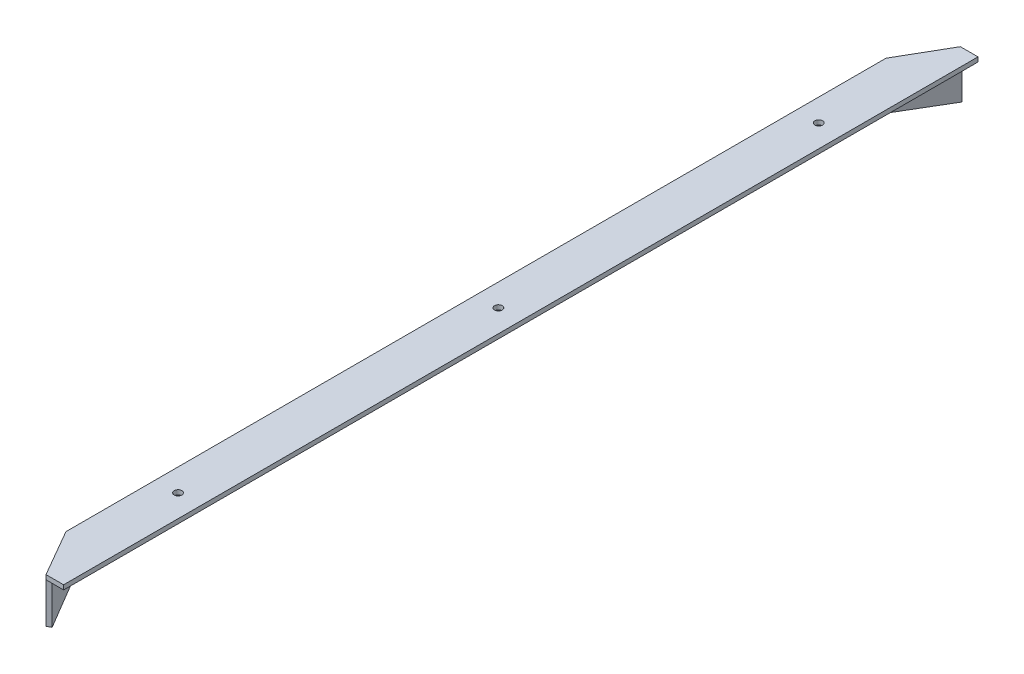
SolidWorks part; units mm, degrees
material "1.0116 (S235J2G3)"
ref_plane "Front Plane" through (0, 0, 0) normal (0, 0, 1) x (1, 0, 0)
ref_plane "Top Plane" through (0, 0, 0) normal (0, 1, 0) x (1, 0, 0)
ref_plane "Right Plane" through (0, 0, 0) normal (1, 0, 0) x (0, 0, -1)
sketch "Sketch1" plane through (0, 0, 0) normal (0, 0, 1) x (1, 0, 0)
  line L6 (0, 0) -> (0, 70)
  line L7 (0, 70) -> (70, 70)
  line L8 (70, 70) -> (70, 63)
  line L9 (70, 63) -> (7, 63)
  line L10 (7, 63) -> (7, 0)
  line L11 (7, 0) -> (0, 0)
  dimension "D1" = 70
  dimension "D2" = 70
  dimension "D3" = 7
  dimension "D4" = 7
extrude "Boss-Extrude1" add sketch "Sketch1" along normal blind 640
sketch "Sketch21" plane through (0, 0, 0) normal (0, 0, -1) x (-1, 0, 0)
  line L0 (0, 70) -> (-70, 70) construction
  line L1 (-70, 70) -> (-70, 0) construction
  line L2 (-70, 0) -> (0, 0) construction
  line L3 (0, 0) -> (0, 69.2595) construction
sketch "Sketch22" plane through (0, 70, 0) normal (0, 1, 0) x (1, 0, 0)
  line L0 (70, 0) -> (0, 0) construction
  line L1 (0, -38.5) -> (0, 38.5) construction
  circle A0 centre (35, 0) radius 6
  circle A1 centre (35, 500) radius 6
  circle A2 centre (35, -500) radius 6
  dimension "D1" = 12
  dimension "D2" = 12
  dimension "D3" = 12
  dimension "D4" = 500
  dimension "D5" = 500
  dimension "D6" = 35
  dimension "D7" = 35
extrude "Cut-Extrude4" cut sketch "Sketch22" against normal blind 10
sketch "Sketch23" plane through (0, 0, 0) normal (0, 1, 0) x (1, 0, 0)
  line L0 (0, -640) -> (42.5, -713.6122)
  line L1 (42.5, -713.6122) -> (48.5622, -710.1122)
  line L2 (48.5622, -710.1122) -> (7, -640)
  line L3 (7, -640) -> (0, -640)
  line L4 (0, -38.5) -> (0, 38.5) construction
  dimension "D1" = 7
  dimension "D2" = 210
  dimension "D3" = 85
extrude "Boss-Extrude2" add sketch "Sketch23" along normal blind 63
sketch "Sketch25" plane through (0, 63, 0) normal (0, 1, 0) x (1, 0, 0)
  line L0 (70, -640) -> (0, -640)
  line L1 (70, -640) -> (70, 0) construction
  line L2 (7, -640) -> (70, -640) construction
  line L3 (0, -640) -> (42.5, -713.6122) construction
  line L4 (0, -640) -> (42.5, -713.6122)
  line L5 (42.5, -713.6122) -> (48.5622, -710.1122) construction
  line L6 (42.5, -713.6122) -> (70, -713.6122)
  line L7 (70, -713.6122) -> (70, -640)
extrude "Boss-Extrude3" add sketch "Sketch25" along normal blind 7
mirror "Mirror1" about plane through (0, 0, 0) normal (0, 0, 1) of bodies 113 116
